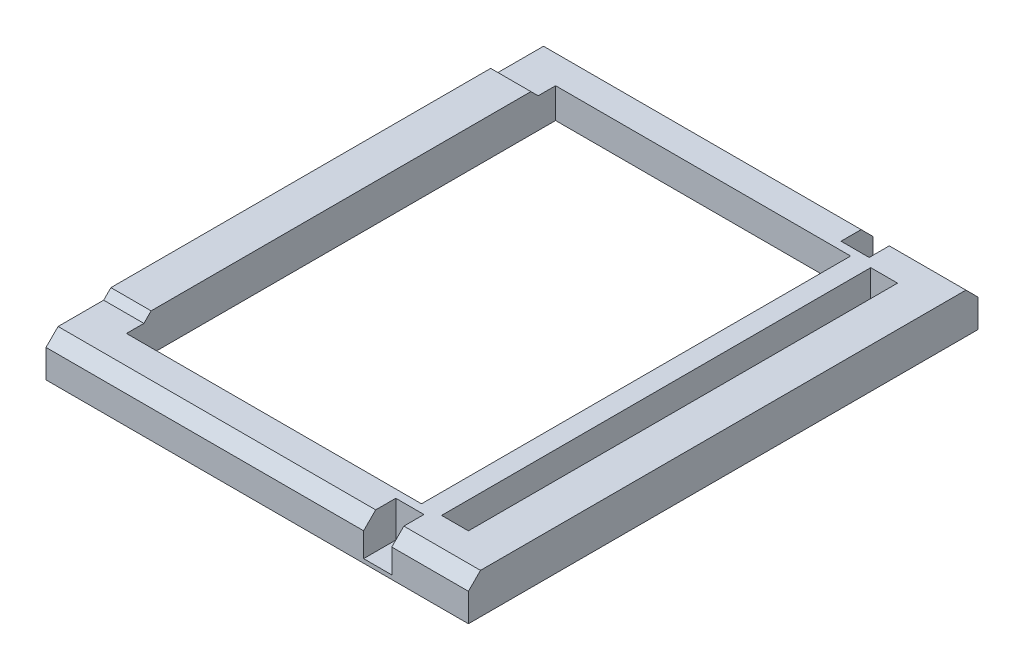
SolidWorks part; units mm, degrees
ref_plane "Front Plane" through (0, 0, 0) normal (0, 0, 1) x (1, 0, 0)
ref_plane "Top Plane" through (0, 0, 0) normal (0, 1, 0) x (1, 0, 0)
ref_plane "Right Plane" through (0, 0, 0) normal (1, 0, 0) x (0, 0, -1)
sketch "Sketch2" plane through (0, 0, 0) normal (0, 1, 0) x (1, 0, 0)
  line L0 (39.1583, 67.7333) -> (39.1583, -67.7333)
  line L1 (-66.675, -80.4333) -> (66.675, -80.4333)
  line L2 (-66.675, -80.4333) -> (-66.675, 80.4333)
  line L3 (-66.675, 80.4333) -> (66.675, 80.4333)
  line L4 (66.675, -80.4333) -> (66.675, 80.4333)
  line L5 (53.975, -67.7333) -> (45.5083, -67.7333)
  line L6 (53.975, -67.7333) -> (53.975, 67.7333)
  line L7 (53.975, 67.7333) -> (45.5083, 67.7333)
  line L8 (-53.975, -67.7333) -> (-53.975, 67.7333)
  line L9 (45.5083, -67.7333) -> (45.5083, 67.7333)
  line L10 (39.1583, 67.7333) -> (-53.975, 67.7333)
  line L11 (39.1583, -67.7333) -> (-53.975, -67.7333)
  point P4 (-66.675, 0)
  point P9 (0, -80.4333)
  point P11 (53.975, 0)
  dimension "D1" = 12.7
  dimension "D2" = 12.7
  dimension "D3" = 160.8667
  dimension "D4" = 133.35
  dimension "D5" = 8.4667
  dimension "D6" = 6.35
  dimension "D7" = 12.7
extrude "Boss-Extrude1" add sketch "Sketch2" along normal blind 12.7
sketch "Sketch3" plane through (0, 0, 0) normal (0, -1, 0) x (1, 0, 0)
  line L0 (-57.15, 76.2) -> (-60.325, 73.025)
  line L1 (-57.15, 76.2) -> (-60.325, 79.375)
  line L2 (-60.325, 73.025) -> (-63.5, 76.2)
  line L3 (-60.325, 79.375) -> (-63.5, 76.2)
  line L4 (-57.15, 76.2) -> (-63.5, 76.2) construction
  line L5 (-60.325, 73.025) -> (-60.325, 79.375) construction
  line L6 (57.15, 76.2) -> (53.975, 73.025)
  line L7 (57.15, 76.2) -> (53.975, 79.375)
  line L8 (53.975, 73.025) -> (50.8, 76.2)
  line L9 (53.975, 79.375) -> (50.8, 76.2)
  line L10 (57.15, 76.2) -> (50.8, 76.2) construction
  line L11 (53.975, 73.025) -> (53.975, 79.375) construction
  line L12 (63.5, -76.2) -> (60.325, -79.375)
  line L13 (63.5, -76.2) -> (60.325, -73.025)
  line L14 (60.325, -79.375) -> (57.15, -76.2)
  line L15 (60.325, -73.025) -> (57.15, -76.2)
  line L16 (63.5, -76.2) -> (57.15, -76.2) construction
  line L17 (60.325, -79.375) -> (60.325, -73.025) construction
  line L18 (-57.15, -76.2) -> (-60.325, -79.375)
  line L19 (-57.15, -76.2) -> (-60.325, -73.025)
  line L20 (-60.325, -79.375) -> (-63.5, -76.2)
  line L21 (-60.325, -73.025) -> (-63.5, -76.2)
  line L22 (-57.15, -76.2) -> (-63.5, -76.2) construction
  line L23 (-60.325, -79.375) -> (-60.325, -73.025) construction
  line L24 (-66.675, -80.4333) -> (-66.675, 80.4333) construction
  line L25 (66.675, -80.4333) -> (-66.675, -80.4333) construction
  line L26 (66.675, 80.4333) -> (66.675, -80.4333) construction
  line L27 (66.675, 80.4333) -> (66.675, -80.4333) construction
  line L28 (-66.675, 80.4333) -> (66.675, 80.4333) construction
  point P1 (-60.325, 76.2)
  point P2 (53.975, 76.2)
  point P3 (60.325, -76.2)
  point P8 (-60.325, -76.2)
  dimension "D1" = 6.35
  dimension "D2" = 4.2333
  dimension "D3" = 6.35
  dimension "D4" = 6.35
  dimension "D5" = 4.2333
  dimension "D6" = 12.7
extrude "Cut-Extrude1" cut sketch "Sketch3" against normal blind 6.35
chamfer "Chamfer4" distance 3.81 angle 45 2 edges at (0, 12.7, -80.4333) (0, 12.7, 80.4333)
chamfer "Chamfer1" distance 0.635 angle 45 32 edges at (-58.7375, 6.35, -77.7875) (-61.9125, 6.35, -77.7875) (-61.9125, 6.35, -74.6125) (-58.7375, 6.35, -74.6125) (55.5625, 6.35, 74.6125) (52.3875, 6.35, 74.6125) (52.3875, 6.35, 77.7875) (55.5625, 6.35, 77.7875) (-58.7375, 6.35, 74.6125) (-61.9125, 6.35, 74.6125) (-61.9125, 6.35, 77.7875) (-58.7375, 6.35, 77.7875) (-58.7375, 0, -74.6125) (-58.7375, 0, -77.7875) (-61.9125, 0, -77.7875) (-61.9125, 0, -74.6125) (58.7375, 0, -77.7875) (58.7375, 0, -74.6125) (61.9125, 0, -74.6125) (61.9125, 0, -77.7875) (61.9125, 6.35, -77.7875) (58.7375, 6.35, -77.7875) (61.9125, 6.35, -74.6125) (58.7375, 6.35, -74.6125) (52.3875, 0, 74.6125) (55.5625, 0, 74.6125) (55.5625, 0, 77.7875) (52.3875, 0, 77.7875) (-61.9125, 0, 74.6125) (-58.7375, 0, 74.6125) (-58.7375, 0, 77.7875) (-61.9125, 0, 77.7875)
chamfer "Chamfer2" distance 3.175 angle 45 6 edges at (49.7417, 0, -67.7333) (49.7417, 0, 67.7333) (53.975, 0, 0) (-7.4083, 0, 67.7333) (-53.975, 0, 0) (-7.4083, 0, -67.7333)
sketch "Sketch4" plane through (0, 0, 80.4333) normal (0, 0, 1) x (1, 0, 0)
  line L1 (33.5915, 1.27) -> (42.4815, 1.27)
  line L2 (33.5915, 1.27) -> (33.5915, 12.7)
  line L3 (33.5915, 12.7) -> (42.4815, 12.7)
  line L4 (42.4815, 1.27) -> (42.4815, 12.7)
  line L6 (66.675, 8.89) -> (66.675, 0) construction
  line L7 (-66.675, 12.7) -> (66.675, 12.7) construction
  dimension "D1" = 8.89
  dimension "D2" = 11.43
  dimension "D3" = 24.1935
extrude "Cut-Extrude2" cut sketch "Sketch4" against normal offset from surface (10.16 mm away) 2.54 up to face at (49.7417, 7.9375, 67.7333)
sketch "Sketch5" plane through (0, 0, -80.4333) normal (0, 0, -1) x (-1, 0, 0)
  line L0 (-33.5915, 8.89) -> (-33.5915, 1.27) construction
  line L1 (-33.5915, 1.27) -> (-42.4815, 1.27)
  line L2 (-33.5915, 1.27) -> (-33.5915, 12.7)
  line L3 (-33.5915, 12.7) -> (-42.4815, 12.7)
  line L4 (-42.4815, 1.27) -> (-42.4815, 12.7)
  line L5 (-42.4815, 12.7) -> (-33.5915, 12.7) construction
  line L8 (-33.5915, 1.27) -> (-42.4815, 1.27) construction
extrude "Cut-Extrude3" cut sketch "Sketch5" against normal offset from surface (10.16 mm away) 2.54 up to face at (49.7417, 7.9375, -67.7333)
sketch "Sketch6" plane through (0, 12.7, 0) normal (0, 1, 0) x (1, 0, 0)
  line L0 (-53.975, 67.7333) -> (-53.975, -67.7333) construction
  line L1 (-53.975, 62.23) -> (-66.675, 62.23)
  line L2 (-53.975, 62.23) -> (-53.975, -62.23)
  line L3 (-53.975, -62.23) -> (-66.675, -62.23)
  line L4 (-66.675, 62.23) -> (-66.675, -62.23)
  line L5 (-66.675, 76.6233) -> (-66.675, -76.6233) construction
  point P8 (-53.975, 0)
  dimension "D1" = 124.46
extrude "Boss-Extrude2" add sketch "Sketch6" along normal blind 2.286
chamfer "Chamfer5" distance 2.286 angle 45 2 edges at (-60.325, 14.986, -62.23) (-60.325, 14.986, 62.23)
